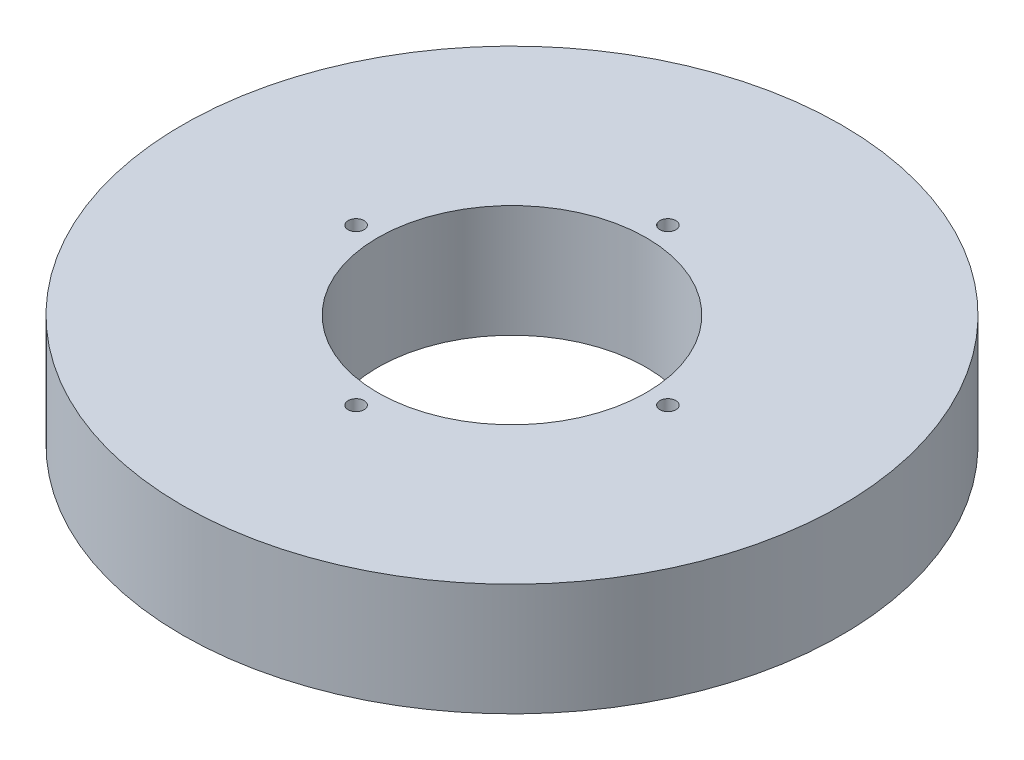
SolidWorks part; units mm, degrees
ref_plane "Front Plane" through (0, 0, 0) normal (0, 0, 1) x (1, 0, 0)
ref_plane "Top Plane" through (0, 0, 0) normal (0, 1, 0) x (1, 0, 0)
ref_plane "Right Plane" through (0, 0, 0) normal (1, 0, 0) x (0, 0, -1)
sketch "Sketch1" plane through (0, 0, 0) normal (0, 1, 0) x (1, 0, 0)
  circle A0 centre (0, 0) radius 67.5
  dimension "FLANGE_OD" = 135
extrude "Boss-Extrude1" add sketch "Sketch1" along normal blind 23
sketch "Sketch2" plane through (0, 0, 0) normal (0, 1, 0) x (1, 0, 0)
  circle A0 centre (0, 0) radius 27.5
  dimension "BORE_D" = 55
extrude "Cut-Extrude1" cut sketch "Sketch2" along normal through all
sketch "Sketch3" plane through (0, 23, 0) normal (0, 1, 0) x (1, 0, 0)
  circle A0 centre (0, 0) radius 31.9312 construction
  circle A1 centre (-31.9312, 0) radius 1.637
  dimension "BOLT_D" = 3.2739
  dimension "BOLT_PCD" = 63.8624
extrude "Cut-Extrude2" cut sketch "Sketch3" against normal blind 22.2385
pattern_circular "CirPattern1" count 4 over 360 about axis through (0, 0, 0) along (0, 1, 0) of "Cut-Extrude2"
